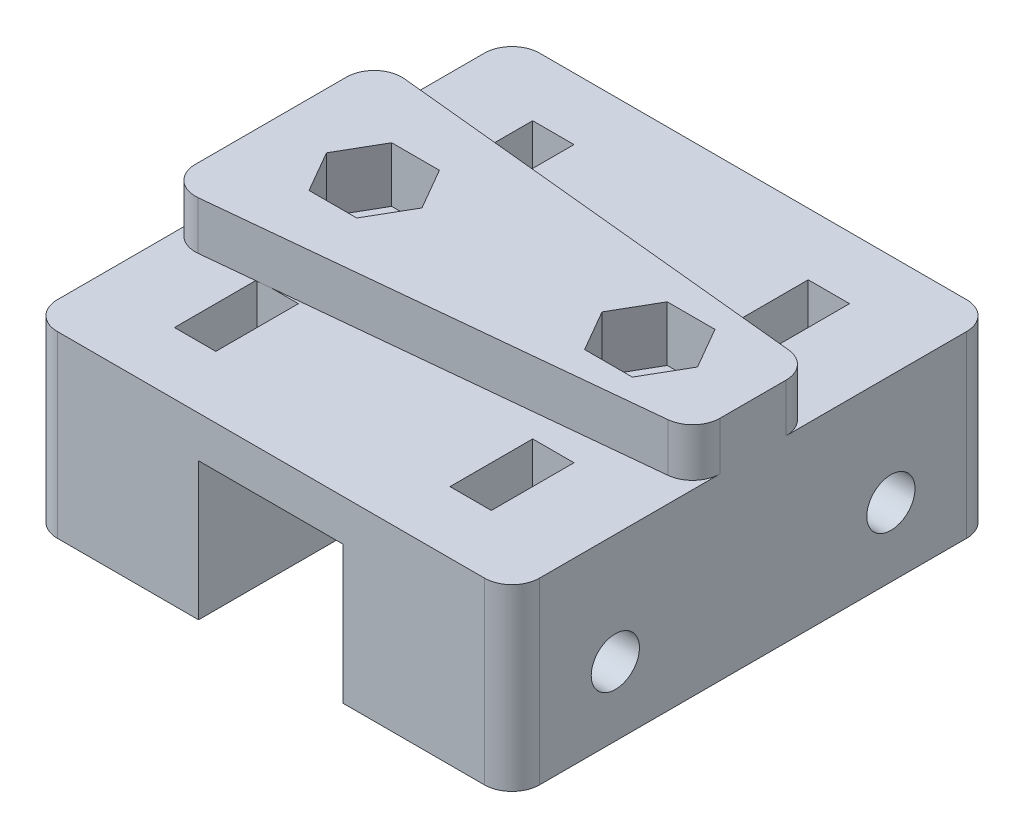
SolidWorks part; units mm, degrees
ref_plane "Спереди" through (0, 0, 0) normal (0, 0, 1) x (1, 0, 0)
ref_plane "Сверху" through (0, 0, 0) normal (0, 1, 0) x (1, 0, 0)
ref_plane "Справа" through (0, 0, 0) normal (1, 0, 0) x (0, 0, -1)
sketch "Эскиз1" plane through (0, 0, 0) normal (0, 1, 0) x (1, 0, 0)
  line L0 (-17.5, 7.5) -> (-17.5, -7.5)
  line L5 (-17.5, -7.5) -> (17.5, -4)
  line L6 (17.5, -4) -> (17.5, 4)
  line L7 (-17.5, 7.5) -> (17.5, 4)
  line L9 (-17.5, 0) -> (17.5, 0) construction
  line L10 (17.5, 0) -> (18.4404, 4.7489) construction
  line L12 (-5.25, 17.5) -> (5.25, 17.5) construction
  line L13 (-5.25, 17.5) -> (-5.25, -17.5)
  line L14 (-5.25, -17.5) -> (5.25, -17.5) construction
  line L15 (5.25, 17.5) -> (5.25, -17.5)
  line L16 (-5.25, 17.5) -> (5.25, -17.5) construction
  line L17 (-5.25, -17.5) -> (5.25, 17.5) construction
  line L21 (-17.5, -17.5) -> (17.5, -17.5)
  line L22 (-17.5, -17.5) -> (-17.5, 17.5)
  line L23 (-17.5, 17.5) -> (17.5, 17.5)
  line L24 (17.5, -17.5) -> (17.5, 17.5)
  line L25 (-17.5, -17.5) -> (17.5, 17.5) construction
  line L26 (-17.5, 17.5) -> (17.5, -17.5) construction
  point P0 (0, 0)
  point P4 (0, 0)
  dimension "D1" = 35
  dimension "D2" = 8
  dimension "D3" = 15
  dimension "D4" = 10.5
  dimension "D5" = 35
extrude "Бобышка-Вытянуть6" add sketch "Эскиз1" along normal blind 3 contours L21 L24 L23 L22
sketch "Эскиз5" plane through (0, 3, 0) normal (0, 1, 0) x (1, 0, 0)
  line L0 (-17.5, 7.5) -> (-17.5, -7.5)
  line L1 (-17.5, -7.5) -> (17.5, -4) construction
  line L2 (17.5, -4) -> (17.5, 4)
  line L3 (17.5, 4) -> (-17.5, 7.5) construction
  line L4 (-17.5, 7.5) -> (-17.5, 7.701)
  line L5 (-17.5, -17.5) -> (-17.5, 17.5) construction
  line L6 (-17.5, -7.5) -> (-17.5, -7.701)
  line L7 (-17.5, -7.701) -> (17.5, -4.201)
  line L8 (17.5, -17.5) -> (17.5, 17.5) construction
  line L9 (17.5, -4.201) -> (17.5, -4)
  line L10 (17.5, 4.201) -> (17.5, 4)
  line L11 (17.5, 4.201) -> (-17.5, 7.701)
  line L12 (17.5, -4) -> (17.5, -4.201)
  line M1 (-17.5, 17.5) -> (-17.5, -17.5)
  line M3 (17.5, -17.5) -> (17.5, 17.5)
  dimension "D1" = 0.2
  dimension "D2" = 0.2
extrude "Бобышка-Вытянуть7" add sketch "Эскиз5" along normal blind 3.5 contours L11 L7 M3 M1 region at (-1.7154, 3, 0)
sketch "Эскиз6" plane through (0, 0, 0) normal (0, -1, 0) x (1, 0, 0)
  line L1 (-17.5, -17.5) -> (-5.25, -17.5)
  line L2 (-17.5, -17.5) -> (-17.5, 17.5)
  line L3 (-17.5, 17.5) -> (-5.25, 17.5)
  line L4 (-5.25, -17.5) -> (-5.25, 17.5)
  line L5 (5.25, 17.5) -> (17.5, 17.5)
  line L6 (5.25, 17.5) -> (5.25, -17.5)
  line L7 (5.25, -17.5) -> (17.5, -17.5)
  line L8 (17.5, 17.5) -> (17.5, -17.5)
extrude "Бобышка-Вытянуть8" add sketch "Эскиз6" along normal blind 10
fillet "Скругление2" radius 2 8 edges at (17.5, -3.5, -17.5) (17.5, -3.5, 17.5) (-17.5, -3.5, -17.5) (-17.5, -3.5, 17.5) (17.5, 4.75, 4.201) (17.5, 4.75, -4.201) (-17.5, 4.75, -7.701) (-17.5, 4.75, 7.701)
sketch "Эскиз7" plane through (-17.5, 0, 0) normal (-1, 0, 0) x (0, 0, 1)
  line L0 (-15.5, -10) -> (-15.5, 0) construction
  line L1 (17.5, 0) -> (-17.5, 0) construction
  line L2 (-15.5, 3) -> (-15.5, -10) construction
  line L3 (-15.5, -5) -> (15.5, -5) construction
  line L4 (15.5, -10) -> (15.5, 3) construction
  circle A0 centre (-10, -5) radius 1.75
  circle A1 centre (0, -5) radius 1.75 construction
  circle A2 centre (10, -5) radius 1.75
  dimension "D1" = 3.5
  dimension "D2" = 3.5
  dimension "D3" = 3.5
  dimension "D4" = 10
  dimension "D5" = 10
sketch "Эскиз8" plane through (0, -10, 0) normal (0, -1, 0) x (1, 0, 0)
  line L0 (-17.5, 0) -> (17.5, 0) construction
  line L1 (17.5, -15.5) -> (17.5, 15.5) construction
  line L2 (-11.5, -7) -> (-8.5, -7)
  line L3 (-11.5, 3) -> (-8.5, 3) construction
  line L4 (-11.5, 3) -> (-11.5, -3) construction
  line L5 (-11.5, -3) -> (-8.5, -3) construction
  line L6 (-8.5, 3) -> (-8.5, -3) construction
  line L7 (-11.5, 3) -> (-8.5, -3) construction
  line L8 (-11.5, -3) -> (-8.5, 3) construction
  line L9 (8.5, 3) -> (11.5, 3) construction
  line L10 (8.5, 3) -> (8.5, -3) construction
  line L11 (8.5, -3) -> (11.5, -3) construction
  line L12 (11.5, 3) -> (11.5, -3) construction
  line L13 (8.5, 3) -> (11.5, -3) construction
  line L14 (8.5, -3) -> (11.5, 3) construction
  line L15 (-11.5, -7) -> (-11.5, -13)
  line L16 (-11.5, -13) -> (-8.5, -13)
  line L17 (-8.5, -7) -> (-8.5, -13)
  line L18 (8.5, -7) -> (11.5, -7)
  line L19 (8.5, -7) -> (8.5, -13)
  line L20 (8.5, -13) -> (11.5, -13)
  line L21 (11.5, -7) -> (11.5, -13)
  line L22 (-17.5, -10) -> (17.5, -10) construction
  line L23 (-11.5, -7) -> (-8.5, -13) construction
  line L24 (-11.5, -13) -> (-8.5, -7) construction
  line L25 (8.5, -7) -> (11.5, -13) construction
  line L26 (8.5, -13) -> (11.5, -7) construction
  line L27 (-11.5, 3) -> (-8.5, 3)
  line L28 (-11.5, 3) -> (-11.5, -3)
  line L29 (-11.5, -3) -> (-8.5, -3)
  line L30 (-8.5, 3) -> (-8.5, -3)
  line L31 (8.5, 3) -> (11.5, 3)
  line L32 (8.5, 3) -> (8.5, -3)
  line L33 (8.5, -3) -> (11.5, -3)
  line L34 (11.5, 3) -> (11.5, -3)
  line L35 (-17.5, 0) -> (17.5, 0) construction
  line L36 (-11.5, 3) -> (-8.5, -3) construction
  line L37 (-11.5, -3) -> (-8.5, 3) construction
  line L38 (8.5, 3) -> (11.5, -3) construction
  line L39 (8.5, -3) -> (11.5, 3) construction
  line L40 (-11.5, 13) -> (-8.5, 13)
  line L41 (-11.5, 13) -> (-11.5, 7)
  line L42 (-11.5, 7) -> (-8.5, 7)
  line L43 (-8.5, 13) -> (-8.5, 7)
  line L44 (8.5, 13) -> (11.5, 13)
  line L45 (8.5, 13) -> (8.5, 7)
  line L46 (8.5, 7) -> (11.5, 7)
  line L47 (11.5, 13) -> (11.5, 7)
  line L48 (-17.5, 10) -> (17.5, 10) construction
  line L49 (-11.5, 13) -> (-8.5, 7) construction
  line L50 (-11.5, 7) -> (-8.5, 13) construction
  line L51 (8.5, 13) -> (11.5, 7) construction
  line L52 (8.5, 7) -> (11.5, 13) construction
  point P0 (-10, 0)
  point P6 (0, 0)
  point P12 (10, 0)
  point P18 (-10, -10)
  point P22 (0, -10)
  point P27 (10, -10)
  point P32 (-10, 0)
  point P35 (0, 0)
  point P40 (10, 0)
  point P45 (-10, 10)
  point P48 (0, 10)
  point P53 (10, 10)
  dimension "D1" = 3
  dimension "D2" = 3
  dimension "D3" = 6
  dimension "D4" = 6
  dimension "D5" = 10
  dimension "D6" = 10
  dimension "D7" = 2
  dimension "D8" = 2
extrude "Вырез-Вытянуть3" cut sketch "Эскиз7" against normal through all
extrude "Вырез-Вытянуть4" cut sketch "Эскиз8" against normal up to surface (13 mm away) contours L21 L18 L19 L20 | L17 L16 L15 L2 | L43 L42 L41 L40 | L47 L46 L45 L44 | L10 L9 L12 L11 region at (10, -10, -10) up to face at (0.0425, 3, -10.9259)
sketch "Эскиз11" plane through (0, 6.5, 0) normal (0, 1, 0) x (1, 0, 0)
  line L0 (-10, 0) -> (10, 0) construction
  line L1 (-8.2679, -3) -> (-6.5359, 0)
  line L2 (-6.5359, 0) -> (-8.2679, 3)
  line L3 (-8.2679, 3) -> (-11.7321, 3)
  line L4 (-11.7321, 3) -> (-13.4641, 0)
  line L5 (-13.4641, 0) -> (-11.7321, -3)
  line L6 (-11.7321, -3) -> (-8.2679, -3)
  line L7 (6.5359, 0) -> (8.2679, -3)
  line L8 (8.2679, -3) -> (11.7321, -3)
  line L9 (11.7321, -3) -> (13.4641, 0)
  line L10 (13.4641, 0) -> (11.7321, 3)
  line L11 (11.7321, 3) -> (8.2679, 3)
  line L12 (8.2679, 3) -> (6.5359, 0)
  line L15 (-10, 13) -> (-10, -13) construction
  line L16 (-8.5, 13) -> (-11.5, 13) construction
  line L17 (-8.5, -13) -> (-11.5, -13) construction
  circle A0 centre (-10, 0) radius 3 construction
  circle A1 centre (10, 0) radius 3 construction
  point P9 (-10, 0)
  point P20 (10, 0)
  point P21 (6.5359, 0)
  point P26 (0, 0)
  dimension "D1" = 6
  dimension "D2" = 6
extrude "Вырез-Вытянуть5" cut sketch "Эскиз11" against normal blind 4
sketch "Эскиз12" plane through (0, 2.5, 0) normal (0, 1, 0) x (1, 0, 0)
  line L0 (-11.7321, 3) -> (-8.2679, -3) construction
  line L1 (-8.2679, -3) -> (-11.7321, -3) construction
  line L2 (-11.7321, -3) -> (-8.2679, 3) construction
  line L3 (-8.2679, 3) -> (-11.7321, 3) construction
  line L4 (7, 1.7321) -> (13, -1.7321) construction
  line L5 (13, -1.7321) -> (13, 1.7321) construction
  line L6 (13, -1.7321) -> (13, 1.7321) construction
  line L7 (13, 1.7321) -> (7, -1.7321) construction
  line L8 (7, -1.7321) -> (7, 1.7321) construction
  circle A0 centre (-10, 0) radius 1.75
  circle A1 centre (10, 0) radius 1.75
  dimension "D1" = 3.5
  dimension "D2" = 3.5
extrude "Вырез-Вытянуть6" cut sketch "Эскиз12" against normal through all
sketch "Эскиз13" plane through (0, -10, 0) normal (0, -1, 0) x (1, 0, 0)
  line L0 (5.25, -17.5) -> (-5.25, -17.5)
  line L1 (-5.25, 17.5) -> (5.25, 17.5)
  line L2 (11.5, -7) -> (11.5, -13) construction
  line L3 (8.5, -13) -> (11.5, -13) construction
  line L4 (-17.5, 15.5) -> (-17.5, -15.5)
  line L5 (-15.5, -17.5) -> (-5.25, -17.5)
  line L6 (-5.25, -17.5) -> (-5.25, 17.5)
  line L7 (-5.25, 17.5) -> (-15.5, 17.5)
  line L8 (-17.5, 15.5) -> (-17.5, -15.5)
  line L9 (-15.5, -17.5) -> (-5.25, -17.5)
  line L10 (-5.25, -17.5) -> (-5.25, 17.5)
  line L11 (-5.25, 17.5) -> (-15.5, 17.5)
  line L12 (5.25, -17.5) -> (15.5, -17.5)
  line L13 (17.5, -15.5) -> (17.5, 15.5)
  line L14 (15.5, 17.5) -> (5.25, 17.5)
  line L15 (5.25, 17.5) -> (5.25, -17.5)
  line L16 (5.25, -17.5) -> (15.5, -17.5)
  line L17 (17.5, -15.5) -> (17.5, 15.5)
  line L18 (15.5, 17.5) -> (5.25, 17.5)
  line L19 (5.25, 17.5) -> (5.25, -17.5)
  line L20 (8.5, -7) -> (8.5, -13) construction
  line L21 (8.5, -7) -> (11.5, -7) construction
  line L22 (8.5, 7) -> (11.5, 7) construction
  line L23 (11.5, 13) -> (11.5, 7) construction
  line L24 (8.5, 13) -> (11.5, 13) construction
  line L25 (8.5, 13) -> (8.5, 7) construction
  line L26 (-11.5, 7) -> (-8.5, 7) construction
  line L27 (-8.5, 13) -> (-8.5, 7) construction
  line L28 (-11.5, 13) -> (-8.5, 13) construction
  line L29 (-11.5, 13) -> (-11.5, 7) construction
  line L30 (-11.5, -13) -> (-8.5, -13) construction
  line L31 (-8.5, -7) -> (-8.5, -13) construction
  line L32 (-11.5, -7) -> (-8.5, -7) construction
  line L33 (-11.5, -7) -> (-11.5, -13) construction
  line L34 (11.5, -7) -> (11.5, -13)
  line L35 (8.5, -13) -> (11.5, -13)
  line L36 (8.5, -7) -> (8.5, -13)
  line L37 (8.5, -7) -> (11.5, -7)
  line L38 (8.5, 7) -> (11.5, 7)
  line L39 (11.5, 13) -> (11.5, 7)
  line L40 (8.5, 13) -> (11.5, 13)
  line L41 (8.5, 13) -> (8.5, 7)
  line L42 (-11.5, 7) -> (-8.5, 7)
  line L43 (-8.5, 13) -> (-8.5, 7)
  line L44 (-11.5, 13) -> (-8.5, 13)
  line L45 (-11.5, 13) -> (-11.5, 7)
  line L46 (-11.5, -13) -> (-8.5, -13)
  line L47 (-8.5, -7) -> (-8.5, -13)
  line L48 (-11.5, -7) -> (-8.5, -7)
  line L49 (-11.5, -7) -> (-11.5, -13)
  circle A0 centre (10, 0) radius 1.75 construction
  circle A1 centre (-10, 0) radius 1.75 construction
  arc A2 (-17.5, -15.5) -> (-15.5, -17.5) centre (-15.5, -15.5) ccw
  arc A3 (-15.5, 17.5) -> (-17.5, 15.5) centre (-15.5, 15.5) ccw
  arc A4 (-17.5, -15.5) -> (-15.5, -17.5) centre (-15.5, -15.5) ccw
  arc A5 (-15.5, 17.5) -> (-17.5, 15.5) centre (-15.5, 15.5) ccw
  arc A6 (15.5, -17.5) -> (17.5, -15.5) centre (15.5, -15.5) ccw
  arc A7 (17.5, 15.5) -> (15.5, 17.5) centre (15.5, 15.5) ccw
  arc A8 (15.5, -17.5) -> (17.5, -15.5) centre (15.5, -15.5) ccw
  arc A9 (17.5, 15.5) -> (15.5, 17.5) centre (15.5, 15.5) ccw
  circle A10 centre (10, 0) radius 1.75
  circle A11 centre (-10, 0) radius 1.75
  dimension "D1" = 0
  dimension "D2" = 0
ref_plane "Плоскость1" through (0, 0, 0) normal (0, 0, 1) x (1, 0, 0)
